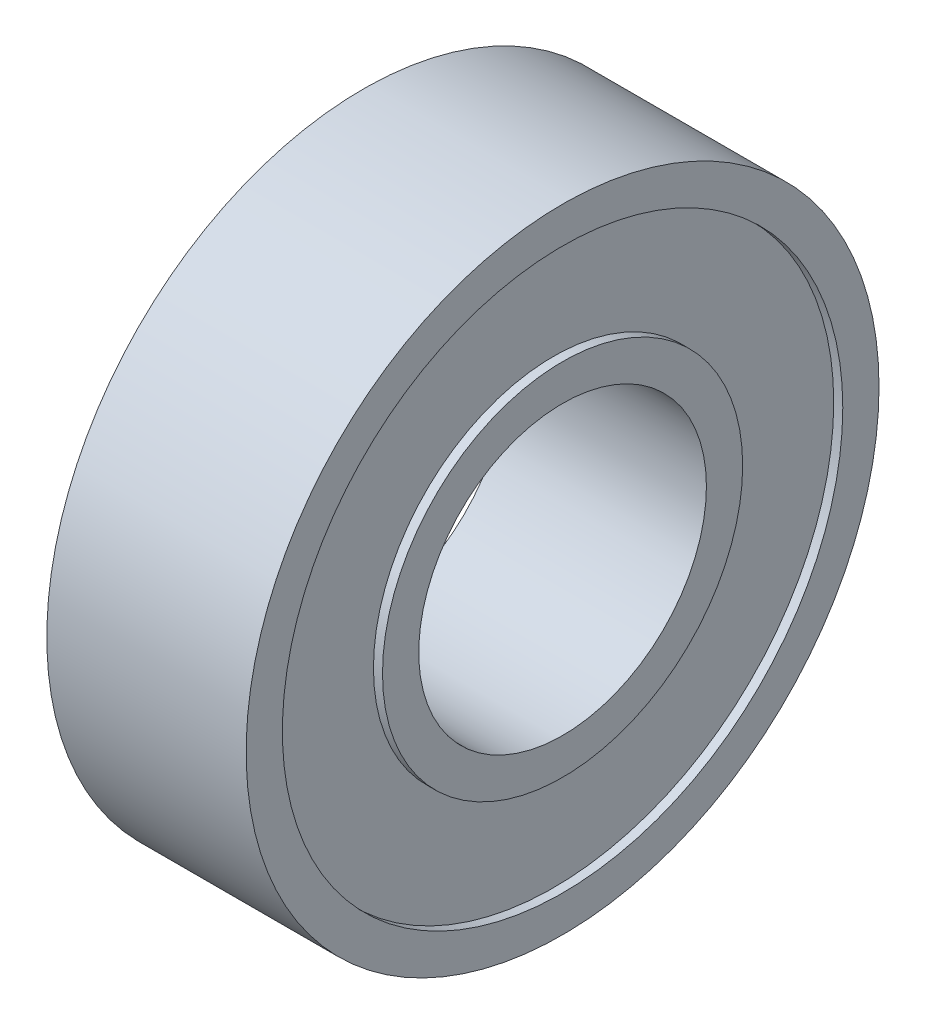
SolidWorks part; units mm, degrees
ref_plane "Front Plane" through (0, 0, 0) normal (0, 0, 1) x (1, 0, 0)
ref_plane "Top Plane" through (0, 0, 0) normal (0, 1, 0) x (1, 0, 0)
ref_plane "Right Plane" through (0, 0, 0) normal (1, 0, 0) x (0, 0, -1)
sketch "Sketch1" plane through (0, 0, 0) normal (0, 0, 1) x (1, 0, 0)
  line L0 (0, 0) -> (-16580.4507, 0) construction
  line L1 (-5.5, 7.9375) -> (5.5, 7.9375)
  line L2 (0, 0) -> (0, 50000) construction
  line L3 (-5.5, 17.4625) -> (5.5, 17.4625)
  line L4 (5.5, 17.4625) -> (5.5, 15.4625)
  line L5 (-5.5, 7.9375) -> (-5.5, 9.9375)
  line L6 (-5.5, 15.4625) -> (-5, 15.4625)
  line L7 (-5, 15.4625) -> (-5, 9.9375)
  line L8 (-5, 9.9375) -> (-5.5, 9.9375)
  line L9 (5.5, 15.4625) -> (5, 15.4625)
  line L10 (5, 15.4625) -> (5, 9.9375)
  line L11 (5, 9.9375) -> (5.5, 9.9375)
  line L12 (-5.5, 15.4625) -> (-5.5, 17.4625)
  line L13 (5.5, 9.9375) -> (5.5, 7.9375)
  dimension "D1" = 11
  dimension "D2" = 15.875
  dimension "D3" = 34.925
  dimension "D4" = 0.5
  dimension "D5" = 2
  dimension "D6" = 2
revolve "Revolve1" add sketch "Sketch1" angle 360 about L0 region at (0, 12.7, 0)
